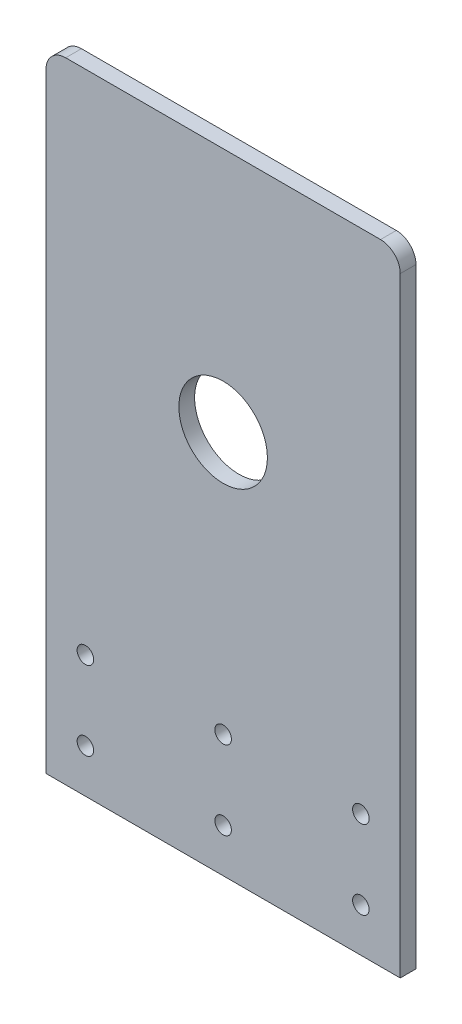
SolidWorks part; units mm, degrees
ref_plane "Front Plane" through (0, 0, 0) normal (0, 0, 1) x (1, 0, 0)
ref_plane "Top Plane" through (0, 0, 0) normal (0, 1, 0) x (1, 0, 0)
ref_plane "Right Plane" through (0, 0, 0) normal (1, 0, 0) x (0, 0, -1)
sketch "Sketch1" plane through (0, 0, 0) normal (0, 0, 1) x (1, 0, 0)
  line L1 (-57.15, -101.6) -> (57.15, -101.6)
  line L2 (-57.15, -101.6) -> (-57.15, 101.6)
  line L3 (-57.15, 101.6) -> (57.15, 101.6)
  line L4 (57.15, -101.6) -> (57.15, 101.6)
  line L5 (-57.15, -101.6) -> (57.15, 101.6) construction
  line L6 (-57.15, 101.6) -> (57.15, -101.6) construction
  point P0 (0, 0)
extrude "Boss-Extrude1" add sketch "Sketch1" along normal blind 5.08
fillet "Fillet1" radius 6.35 2 edges at (-57.15, 101.6, 2.54) (57.15, 101.6, 2.54)
sketch "Sketch3" plane through (0, 0, 5.08) normal (0, 0, 1) x (1, 0, 0)
  line L0 (0, -101.6) -> (0, 22.352)
  line L1 (-57.15, -101.6) -> (57.15, -101.6) construction
  circle A0 centre (0, 22.352) radius 14.2875
extrude "Cut-Extrude1" cut sketch "Sketch3" against normal up to surface (5.08 mm away) contours A0 region at (9.817, 12.535, 5.08) up to face at (0, 32.1884, 0)
sketch "Sketch4" plane through (0, 0, 5.08) normal (0, 0, 1) x (1, 0, 0)
  line L0 (57.15, -101.6) -> (57.15, -87.503)
  line L1 (57.15, -101.6) -> (57.15, 95.25) construction
  line L2 (57.15, -87.503) -> (44.45, -87.503)
  circle A0 centre (44.45, -87.503) radius 2.667
  circle A1 centre (0, -87.503) radius 2.667
  circle A2 centre (-44.45, -87.503) radius 2.667
  circle A3 centre (0, -62.103) radius 2.667
  circle A4 centre (-44.45, -62.103) radius 2.667
  circle A5 centre (44.45, -62.103) radius 2.667
  dimension "D1" = 3
  dimension "D2" = 2
extrude "Cut-Extrude2" cut sketch "Sketch4" against normal up to surface (5.08 mm away) contours A4 | A2 | A3 | A1 | A5 | A0 region at (41.8584, -87.503, 5.08) region at (0, -87.503, 5.08) region at (-44.45, -87.503, 5.08) region at (0, -62.103, 5.08) region at (-44.45, -62.103, 5.08) region at (44.45, -62.103, 5.08) up to face at (-14.2875, 22.352, 0)
